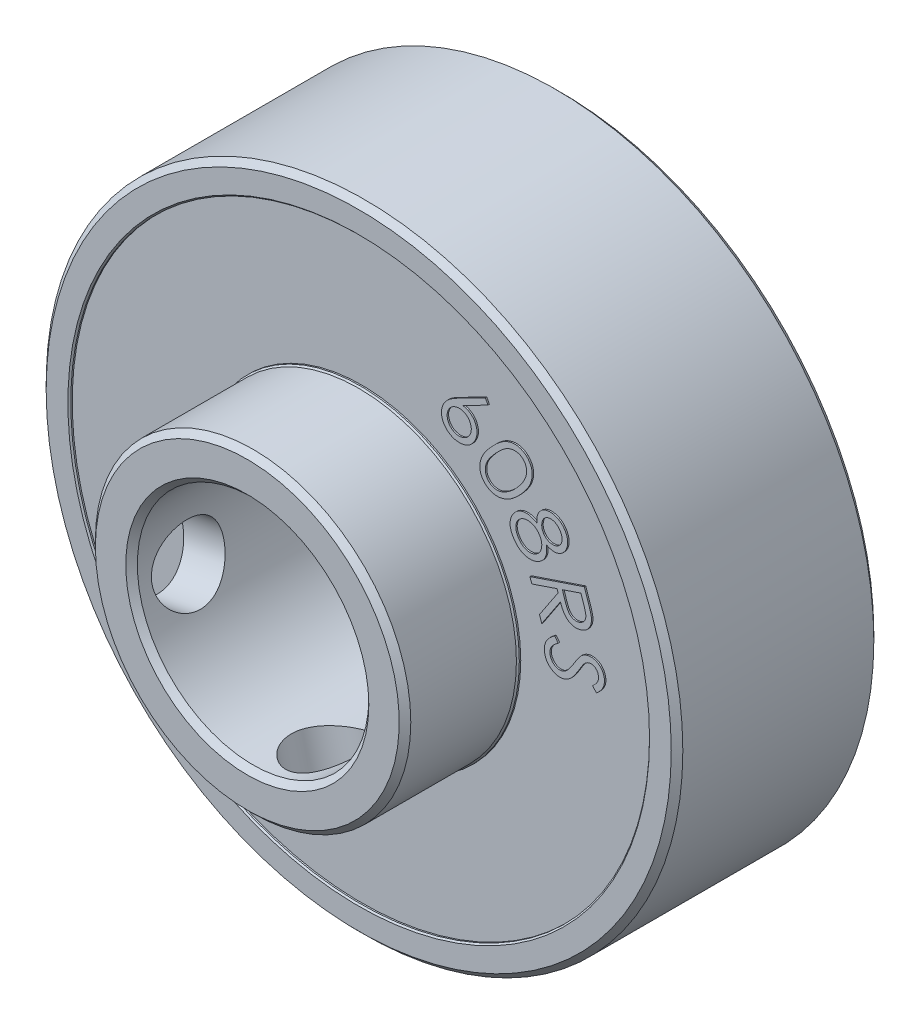
SolidWorks part; units mm, degrees
material "AISI 1020"
ref_plane "Front Plane" through (0, 0, 0) normal (0, 0, 1) x (1, 0, 0)
ref_plane "Top Plane" through (0, 0, 0) normal (0, 1, 0) x (1, 0, 0)
ref_plane "Right Plane" through (0, 0, 0) normal (1, 0, 0) x (0, 0, -1)
sketch "Sketch1" plane through (0, 0, 0) normal (0, 0, 1) x (1, 0, 0)
  circle A0 centre (0, 0) radius 11
  circle A1 centre (0, 0) radius 4
extrude "Boss-Extrude1" add sketch "Sketch1" along normal blind 7
sketch "Sketch2" plane through (0, 0, 7) normal (0, 0, 1) x (1, 0, 0)
  circle A0 centre (0, 0) radius 5.5
  circle A1 centre (0, 0) radius 10
extrude "Cut-Extrude1" cut sketch "Sketch2" against normal blind 0.1
extrude "Cut-Extrude2" cut sketch "Sketch2<2>" against normal blind 0.1 from offset 6.9 offset against normal yes
sketch "Sketch2<2>" plane through (0, 0, 7) normal (0, 0, 1) x (1, 0, 0) same geometry as "Sketch2"
chamfer "Chamfer2" distance 0.05 angle 45 4 edges at (5.5, 0, 7) (10, 0, 7) (10, 0, 0) (5.5, 0, 0)
sketch "Esboço2" plane through (0, 0, 7) normal (0, 0, 1) x (1, 0, 0)
  circle A0 centre (0, 0) radius 5.45
  circle A1 centre (0, 0) radius 4
extrude "Ressalto-extrusão1" add sketch "Esboço2" along normal blind 3.85
sketch "Sketch3" plane through (0, 0, 0.1) normal (0, 0, -1) x (-1, 0, 0)
  circle A0 centre (0, 0) radius 6.5 construction
  text T0 "608RS" font "Century Gothic" height 2
extrude "Boss-Extrude2" add sketch "Sketch3" along normal blind 0.05
chamfer "Chamfer1" distance 0.2 angle 45 5 edges at (4, 0, 0) (11, 0, 7) (11, 0, 0) (5.45, 0, 10.85) (4, 0, 10.85)
sketch "Sketch4" plane through (0, 0, 6.9) normal (0, 0, 1) x (1, 0, 0)
  circle A0 centre (0, 0) radius 6.5 construction
  text T0 "608RS" font "Century Gothic" height 2
extrude "Boss-Extrude3" add sketch "Sketch4" along normal blind 0.05
hole_wizard "Furo roscado de M31" positions "3DSketch1" profile "Esboço3" tap size "M3" standard "ISO"
sketch3d "3DSketch1"
  point P0 (-5.3555, -1.0105, 8.9668)
  point P2 (1.3573, -5.2783, 9.0638)
sketch "Esboço3" plane through (-5.3555, -1.0105, 8.9668) normal (0, 0, 1) x (0.1854, -0.9827, 0)
  line L0 (0, 0) -> (0, 8.2511)
  line L1 (0, 8.2511) -> (1.25, 7.5)
  line L2 (1.25, 7.5) -> (1.25, 0)
  line L5 (1.25, 0) -> (0, 0)
  line L10 (0, 8.2511) -> (-1.25, 7.5) construction
  line L11 (0, -6.35) -> (0, 107.95) construction
  dimension "Tap Drill Dia." = 2.5
  dimension "Tap Drill Depth" = 7.5
  dimension "Drill Angle" = 118
sketch "Sketch5" plane through (0, 0, 0) normal (1, 0, 0) x (0, 0, -1)
  line L0 (0, -10.8) -> (0, 10.8) construction
  circle A0 centre (-3.5, 0) radius 1
  dimension "D1" = 3.5
scale "Scale1" scale about origin uniform scaling yes scale factor 1.25
scale "Scale2" bodies to scale 108 scale about centroid uniform scaling yes scale factor 1.5
